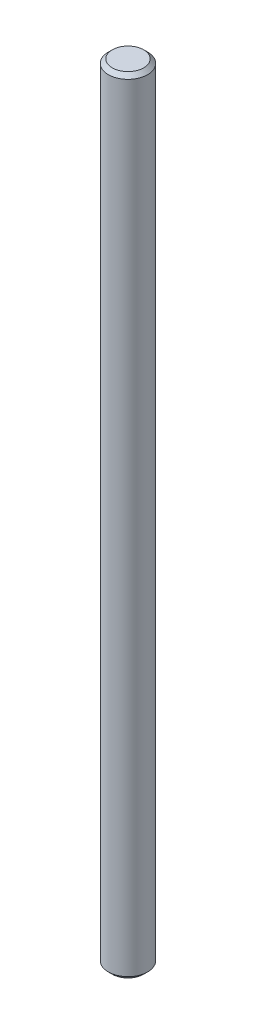
SolidWorks part; units mm, degrees
ref_plane "Front Plane" through (0, 0, 0) normal (0, 0, 1) x (1, 0, 0)
ref_plane "Top Plane" through (0, 0, 0) normal (0, 1, 0) x (1, 0, 0)
ref_plane "Right Plane" through (0, 0, 0) normal (1, 0, 0) x (0, 0, -1)
sketch "Sketch2" plane through (0, 0, 0) normal (0, 1, 0) x (1, 0, 0)
  circle A0 centre (0, 0) radius 2.5
  dimension "D1" = 5
extrude "Boss-Extrude1" add sketch "Sketch2" along normal blind 100
chamfer "Chamfer1" distance 0.5 angle 45 2 edges at (0, 0, 2.5) (0, 100, 2.5)
